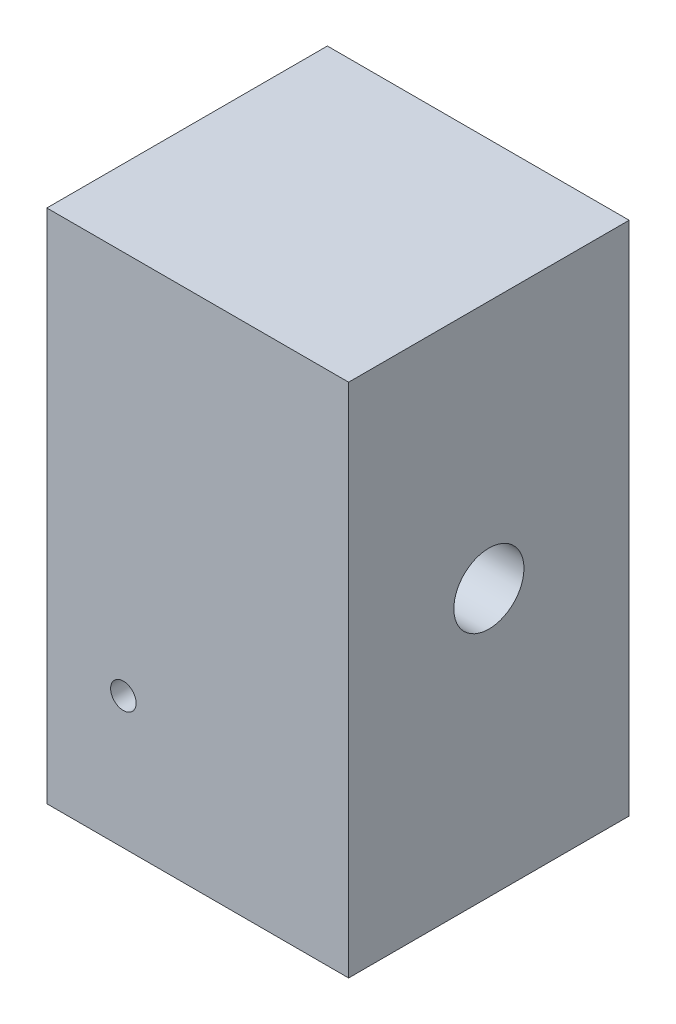
SolidWorks part; units mm, degrees
ref_plane "Front Plane" through (0, 0, 0) normal (0, 0, 1) x (1, 0, 0)
ref_plane "Top Plane" through (0, 0, 0) normal (0, 1, 0) x (1, 0, 0)
ref_plane "Right Plane" through (0, 0, 0) normal (1, 0, 0) x (0, 0, -1)
sketch "Sketch1" plane through (0, 0, 0) normal (0, 0, 1) x (1, 0, 0)
  line L0 (9, 0) -> (9, 4.025)
  line L1 (9, 5.125) -> (13, 5.125)
  line L2 (9, 4.025) -> (13, 5.125)
  line L4 (9, 5.125) -> (9, 4.025)
  line L5 (9, 0) -> (16.8573, 0) construction
  dimension "D2" = 1.1
  dimension "D3" = 4
  dimension "D4" = 9
  dimension "D5" = 4.025
revolve "Revolve1" add sketch "Sketch1" angle 360 about L5
sketch "Sketch2" plane through (0, 0, 0) normal (0, 0, 1) x (1, 0, 0)
  line L0 (0, 0) -> (0, 16.625)
  line L1 (0, 16.625) -> (-2.6, 24.275)
  line L2 (-2.6, 24.275) -> (-7.5, 24.275)
  line L3 (-7.5, 24.275) -> (-7.5, 29.275)
  line L4 (-7.5, 29.275) -> (0, 29.275)
  line L5 (0, 29.275) -> (0, 16.625)
  line L6 (0, 0) -> (-10.3703, 0) construction
  line L7 (0, -12.725) -> (0, -4.625)
  line L8 (0, -12.725) -> (4.5, -12.725)
  line L9 (4.5, -12.725) -> (4.5, -26.425)
  line L10 (4.5, -26.425) -> (-7.5, -26.425)
  line L11 (-7.5, -31.425) -> (13, -31.425)
  line L12 (13, -31.425) -> (13, -4.625)
  line L13 (-7.5, -31.425) -> (-7.5, -26.425)
  line L14 (0, -4.625) -> (0, 0)
  line L15 (0, -4.625) -> (13, -4.625)
  dimension "D1" = 13.7
  dimension "D2" = 8.1
  dimension "D3" = 4.5
  dimension "D4" = 5
  dimension "D5" = 20.5
  dimension "D6" = 5
  dimension "D7" = 2.6
  dimension "D8" = 29.35
  dimension "D9" = 7.65
  dimension "D10" = 13
  dimension "D11" = 4.625
extrude "Boss-Extrude1" add sketch "Sketch2" along normal mid plane 14.1 separate body contours L15 L7 L8 L9 L10 L13 L11 L12 | L5 L4 L3 L2 L1 region at (-3.1456, 25.7165, 0) region at (6.1226, -18.9909, 0)
sketch "Sketch3" plane through (0, 0, 0) normal (1, 0, 0) x (0, 0, -1)
  line L1 (-7.05, 29.275) -> (7.05, 29.275)
  line L2 (-7.05, 29.275) -> (-7.05, -4.625)
  line L3 (-7.05, -4.625) -> (7.05, -4.625)
  line L4 (7.05, 29.275) -> (7.05, -4.625)
extrude "Boss-Extrude7" add sketch "Sketch3" along normal blind 9 contours L4 L2 L1 L3 | L4 L2 L3 region at (0, 12.325, 0)
sketch "Sketch4" plane through (9, 0, 0) normal (1, 0, 0) x (0, 0, -1)
  circle A0 centre (0, 0) radius 3.55
  dimension "D1" = 7.1
extrude "Cut-Extrude1" cut sketch "Sketch4" against normal blind 9
sketch "Sketch5" plane through (9, 0, 0) normal (1, 0, 0) x (0, 0, -1)
  line L1 (-7.05, 29.275) -> (7.05, 29.275)
  line L2 (-7.05, 29.275) -> (-7.05, -4.625)
  line L3 (-7.05, -4.625) -> (7.05, -4.625)
  line L4 (7.05, 29.275) -> (7.05, -4.625)
  circle A0 centre (0, 0) radius 4.125
  dimension "D1" = 8.25
extrude "Boss-Extrude10" add sketch "Sketch5" along normal blind 4
sketch "Sketch6" plane through (13, 0, 0) normal (1, 0, 0) x (0, 0, -1)
  line L0 (-16.5, 29.275) -> (16.5, 29.275)
  line L1 (7.05, 29.275) -> (-7.05, 29.275) construction
  line L2 (0, 29.275) -> (0, -31.425) construction
  line L3 (-7.05, -31.425) -> (7.05, -31.425) construction
  line L4 (-16.5, 29.275) -> (-16.5, -31.425)
  line L5 (-16.5, -31.425) -> (16.5, -31.425)
  line L6 (16.5, 29.275) -> (16.5, -31.425)
  circle A0 centre (0, 0) radius 4.125
  dimension "D2" = 8.25
  dimension "D1" = 16.5
extrude "Boss-Extrude11" add sketch "Sketch6" along normal blind 15
sketch "Sketch7" plane through (13, 0, 0) normal (-1, 0, 0) x (0, 0, 1)
  line L0 (-7.05, 29.275) -> (-16.5, 29.275)
  line L1 (-16.5, 29.275) -> (-16.5, -31.425)
  line L2 (-7.05, -31.425) -> (-16.5, -31.425) construction
  line L3 (-16.5, -31.425) -> (-7.05, -31.425)
  line L4 (-7.05, -31.425) -> (-7.05, 29.275)
  line L5 (0, 29.275) -> (0, -31.425) construction
  line L6 (7.05, 29.275) -> (-7.05, 29.275) construction
  line L7 (7.05, -31.425) -> (-7.05, -31.425) construction
  line L8 (7.05, -31.425) -> (7.05, 29.275)
  line L9 (16.5, -31.425) -> (7.05, -31.425)
  line L10 (16.5, 29.275) -> (16.5, -31.425)
  line L11 (7.05, 29.275) -> (16.5, 29.275)
  dimension "D1" = 9.45
extrude "Boss-Extrude12" add sketch "Sketch7" along normal up to surface (13 mm away) up to face at (0, -5.3875, 1.7625)
sketch "Sketch8" plane through (0, 0, 0) normal (-1, 0, 0) x (0, 0, 1)
  line L0 (0, 29.275) -> (0, -31.425) construction
  line L1 (7.05, 29.275) -> (-7.05, 29.275) construction
  line L2 (7.05, -31.425) -> (-7.05, -31.425) construction
  line L3 (0, 16.625) -> (0, 29.275)
  line L4 (7.05, 16.625) -> (-7.05, 16.625) construction
  line L5 (16.5, 29.275) -> (-16.5, 29.275)
  line L6 (-16.5, 29.275) -> (-16.5, -31.425)
  line L7 (-16.5, -31.425) -> (-7.05, -31.425)
  line L8 (-16.5, -31.425) -> (-7.05, -31.425) construction
  line L9 (-7.05, -31.425) -> (-7.05, -12.725)
  line L10 (-7.05, -12.725) -> (-11.5, -4.025)
  line L11 (-11.5, -4.025) -> (-11.5, 16.625)
  line L12 (-11.5, 16.625) -> (0, 16.625)
  line L13 (11.5, -4.025) -> (11.5, 16.625)
  line L14 (7.05, -12.725) -> (11.5, -4.025)
  line L15 (7.05, -31.425) -> (7.05, -12.725)
  line L16 (16.5, -31.425) -> (7.05, -31.425)
  line L17 (16.5, 29.275) -> (16.5, -31.425)
  line L18 (11.5, 16.625) -> (2.5, 16.625)
  line L19 (2.5, 16.625) -> (2.5, 29.275)
  line M9 (-7.05, 16.625) -> (-7.05, 29.275)
  line M10 (-7.05, 29.275) -> (-16.5, 29.275)
  line M11 (-16.5, 29.275) -> (-16.5, -31.425)
  line M12 (-16.5, -31.425) -> (-7.05, -31.425)
  line M13 (-7.05, -31.425) -> (-7.05, -26.425)
  line M14 (-7.05, -26.425) -> (-7.05, -12.725)
  line M16 (7.05, -12.725) -> (7.05, -26.425)
  line M17 (7.05, -26.425) -> (7.05, -31.425)
  line M18 (7.05, -31.425) -> (16.5, -31.425)
  line M19 (16.5, -31.425) -> (16.5, 29.275)
  line M20 (16.5, 29.275) -> (7.05, 29.275)
  line M21 (7.05, 29.275) -> (7.05, 16.625)
  dimension "D1" = 23
  dimension "D2" = 8.7
  dimension "D3" = 2.5
extrude "Boss-Extrude13" add sketch "Sketch8" along normal up to surface (7.5 mm away) contours L11 L12 L10 M9 M10 M11 M12 M13 M14 | L18 L13 L14 M16 M17 M18 M19 M20 M21 region at (0, -2.2958, -12.4076) region at (0, -2.2958, 12.4076) up to face at (-7.5, -28.925, 0)
sketch "Sketch9" plane through (0, 0, -16.5) normal (0, 0, -1) x (-1, 0, 0)
  line L0 (13.5, 29.275) -> (13.5, -31.425) construction
  line L1 (-28, -31.425) -> (7.5, -31.425) construction
  circle A0 centre (-1.5, -15.925) radius 1.5
  dimension "D3" = 3
  dimension "D1" = 15
  dimension "D2" = 15.5
extrude "Cut-Extrude2" cut sketch "Sketch9" against normal up to surface (33 mm away) up to face at (10.25, -1.075, 16.5)
sketch "Sketch10" plane through (0, 0, 7.05) normal (0, 0, -1) x (-1, 0, 0)
  line L0 (0, 16.625) -> (2.6, 24.275)
  line L1 (2.6, 24.275) -> (7.5, 24.275)
  line L3 (7.5, 24.275) -> (7.5, 16.625)
  line L5 (7.5, 16.625) -> (0, 16.625)
extrude "Boss-Extrude14" add sketch "Sketch10" along normal blind 4.55
sketch "Sketch11" plane through (0, 0, -7.05) normal (0, 0, 1) x (1, 0, 0)
  line L0 (-7.5, 24.275) -> (-7.5, 16.625)
  line L1 (-7.5, 16.625) -> (0, 16.625) construction
  line L2 (-7.5, 24.275) -> (-2.6, 24.275)
  line L3 (-2.6, 24.275) -> (0, 16.625)
  line L4 (-7.5, 16.625) -> (0, 16.625)
extrude "Boss-Extrude15" add sketch "Sketch11" along normal blind 7.05
sketch "Sketch12" plane through (-7.5, 0, 0) normal (-1, 0, 0) x (0, 0, 1)
  line L0 (-7.05, 16.625) -> (-7.05, 29.275) construction
  line L1 (7.05, 29.275) -> (-7.05, 29.275)
  line L2 (7.05, 29.275) -> (7.05, 24.275)
  line L3 (7.05, 24.275) -> (-7.05, 24.275)
  line L4 (-7.05, 29.275) -> (-7.05, 24.275)
extrude "Boss-Extrude16" add sketch "Sketch12" along normal up to surface (6 mm away) rebuild error yes up to face at (-7.5, 2.3917, 0.4167)
sketch "Sketch14" plane through (0, 0, 0) normal (0, 0, 1) x (1, 0, 0)
  line L0 (0, 0) -> (0, 3.55) construction
  line L1 (0, 3.55) -> (5.52, 3.55) construction
  line L2 (5.52, 3.55) -> (20.6567, 29.7676)
  dimension "D1" = 3.55
  dimension "D2" = 5.52
  dimension "D3" = 120
